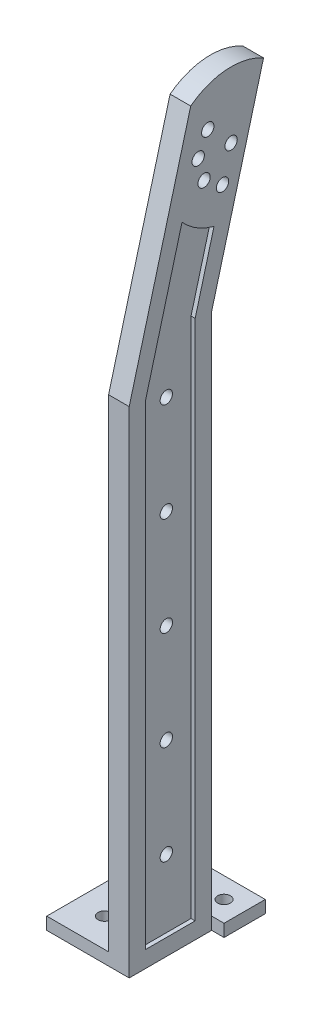
SolidWorks part; units mm, degrees
ref_plane "前视基准面" through (0, 0, 0) normal (0, 0, 1) x (1, 0, 0)
ref_plane "上视基准面" through (0, 0, 0) normal (0, 1, 0) x (1, 0, 0)
ref_plane "右视基准面" through (0, 0, 0) normal (1, 0, 0) x (0, 0, -1)
sketch "草图1" plane through (0, 0, 0) normal (1, 0, 0) x (0, 0, -1)
  line L0 (-10, 0) -> (10, 0)
  line L1 (-10, 0) -> (-10, 120)
  line L2 (10, 0) -> (10, 130)
  line L3 (10, 130) -> (22.5803, 176.9502)
  line L4 (-10, 120) -> (4.9189, 175.6782)
  line L13 (12.6364, 155.294) -> (14.7069, 163.0214) construction
  line L17 (0, 0) -> (0, 120) construction
  circle A9 centre (0, 116.4823) radius 1.5
  arc A10 (22.5803, 176.9502) -> (4.9189, 175.6782) centre (14.7069, 163.0214) ccw
  circle A11 centre (14.7069, 163.0214) radius 1.5
  circle A16 centre (12.6364, 155.294) radius 1.5
  circle A23 centre (0, 92.4823) radius 1.5
  circle A24 centre (0, 68.4823) radius 1.5
  circle A25 centre (0, 44.4823) radius 1.5
  circle A26 centre (0, 20.4823) radius 1.5
  circle A27 centre (8.1537, 158.4328) radius 1.5
  circle A28 centre (6.7374, 163.7186) radius 1.5
  circle A29 centre (9.0501, 168.6782) radius 1.5
  point P3 (0, 0)
  point P29 (14.7069, 163.0214)
  dimension "D5" = 165
  dimension "D7" = 4
  dimension "D4" = 5
  dimension "D9" = 4
  dimension "D11" = 3
  dimension "D6" = 16
  dimension "D8" = 8
  dimension "D1" = 20
  dimension "D2" = 120
  dimension "D3" = 130
extrude "凸台-拉伸2" add sketch "草图1" against normal blind 5
ref_plane "基准面1" through (-5, 0, 0) normal (-1, 0, 0) x (0, 0, 1)
ref_plane "基准面3" through (-30, 0, 0) normal (-1, 0, 0) x (0, 0, 1)
ref_plane "基准面5" through (0, 0, 0) normal (1, 0, 0) x (0, 0, -1)
sketch "草图4" plane through (0, 0, 0) normal (1, 0, 0) x (0, 0, -1)
  line L5 (-6, 119.4734) -> (-6, 4)
  line L6 (-6, 4) -> (6, 4)
  line L7 (6, 4) -> (6, 130.5266)
  line L8 (6, 130.5266) -> (17.8128, 174.6125)
  line L9 (8.4049, 173.2334) -> (-6, 119.4734)
  line L10 (-10, 120) -> (-10, 0)
  line L11 (-10, 0) -> (10, 0)
  line L12 (10, 0) -> (10, 130)
  line L13 (10, 130) -> (22.5803, 176.9502)
  line L14 (4.9189, 175.6782) -> (-10, 120)
  line L15 (-10, 120) -> (-10, 0)
  line L16 (-10, 0) -> (10, 0)
  line L17 (10, 0) -> (10, 130)
  line L18 (10, 130) -> (22.5803, 176.9502)
  line L19 (4.9189, 175.6782) -> (-10, 120)
  arc A1 (17.8128, 174.6125) -> (8.4049, 173.2334) centre (14.7069, 163.0214) ccw
  arc A2 (22.5803, 176.9502) -> (4.9189, 175.6782) centre (14.7069, 163.0214) ccw
  arc A3 (22.5803, 176.9502) -> (4.9189, 175.6782) centre (14.7069, 163.0214) ccw
  arc A4 (2.8038, 152.3296) -> (10.5658, 147.5666) centre (14.7069, 163.0214) ccw
  dimension "D3" = 16
  dimension "D1" = 0
  dimension "D2" = 4
extrude "切除-拉伸1" cut sketch "草图4" against normal blind 1 contours A4 L9 L5 L6 L7 L8 region at (0, 74.1415, -0.4435)
ref_plane "基准面6" through (0, 0, 0) normal (0, -1, 0) x (-1, 0, 0)
sketch "草图5" plane through (0, 0, 0) normal (0, -1, 0) x (-1, 0, 0)
  line L0 (0, -10) -> (20, -10)
  line L1 (20, -10) -> (20, 10)
  line L3 (0, 10) -> (0, -10)
  line L4 (0, 10) -> (-3, 10)
  line L5 (-3, 10) -> (-3, 20)
  line L6 (-3, 20) -> (20, 20)
  line L9 (20, 10) -> (20, 20)
  line L10 (0, -10) -> (0, 10) construction
  dimension "D1" = 20
  dimension "D2" = 20
  dimension "D3" = 20
  dimension "D6" = 3
  dimension "D7" = 10
extrude "凸台-拉伸3" add sketch "草图5" against normal blind 3
sketch "草图6" plane through (0, 0, 0) normal (0, -1, 0) x (1, 0, 0)
  line L0 (-13, 3) -> (-13, -15.9331) construction
  line L1 (-20, 10) -> (0, 10) construction
  line L3 (-20, 10) -> (-20, -20) construction
  line L4 (-20, -20) -> (3, -20) construction
  line L6 (3, -20) -> (3, -10) construction
  circle A1 centre (-13, 3) radius 1.55
  circle A3 centre (-2, -15) radius 1.55
  circle A4 centre (-13, -11) radius 1.55
  dimension "D1" = 3.1
  dimension "D4" = 3.1
  dimension "D2" = 3.1
  dimension "D3" = 14
  dimension "D5" = 7
  dimension "D6" = 7
  dimension "D7" = 5
  dimension "D9" = 5
extrude "切除-拉伸2" cut sketch "草图6" against normal blind 10
sketch "草图7" plane through (-5, 0, 0) normal (-1, 0, 0) x (0, 0, 1)
  line L0 (10, 3) -> (-10, 3) construction
  line L5 (-6.8, 3) -> (-3.8, 3)
  line L6 (-6.8, 3) -> (-6.8, 44)
  line L7 (-6.8, 44) -> (-3.8, 44)
  line L8 (-3.8, 3) -> (-3.8, 44)
  line L9 (-10, 3) -> (-10, 130) construction
  dimension "D1" = 3
  dimension "D2" = 41
  dimension "D3" = 3.2
extrude "凸台-拉伸4" add sketch "草图7" along normal blind 13
sketch "草图9" plane through (0, 0, -6.8) normal (0, 0, -1) x (-1, 0, 0)
  line L0 (18, 44) -> (5, 44) construction
  line L1 (5, 44) -> (18, 44)
  arc A0 (18, 44) -> (5, 44) centre (11.5, 44) ccw
extrude "凸台-拉伸5" add sketch "草图9" against normal blind 3
sketch "草图11" plane through (0, 0, -6.8) normal (0, 0, -1) x (-1, 0, 0)
  line L0 (11.5, 44) -> (11.5, 7) construction
  line L3 (5, 44) -> (5, 3)
  line L4 (5, 3) -> (18, 3)
  line L5 (18, 3) -> (18, 44)
  line L6 (5, 44) -> (5, 3) construction
  line L7 (5, 3) -> (18, 3) construction
  line L8 (18, 3) -> (18, 44) construction
  circle A0 centre (11.5, 44) radius 1.5
  arc A1 (18, 44) -> (5, 44) centre (11.5, 44) ccw
  arc A2 (18, 44) -> (5, 44) centre (11.5, 44) ccw construction
  circle A3 centre (11.5, 7) radius 1.5
  dimension "D2" = 3
  dimension "D3" = 37
  dimension "D1" = 0
extrude "切除-拉伸4" cut sketch "草图11" against normal through all
sketch "草图10" plane through (0, 0, -6.8) normal (0, 0, -1) x (-1, 0, 0)
  circle A0 centre (11.5, 44) radius 1.6
  circle A1 centre (11.5, 7) radius 1.6
  dimension "D1" = 3.2
  dimension "D2" = 3.2
  dimension "D3" = 37
extrude "切除-拉伸3" cut sketch "草图10" against normal blind 3
